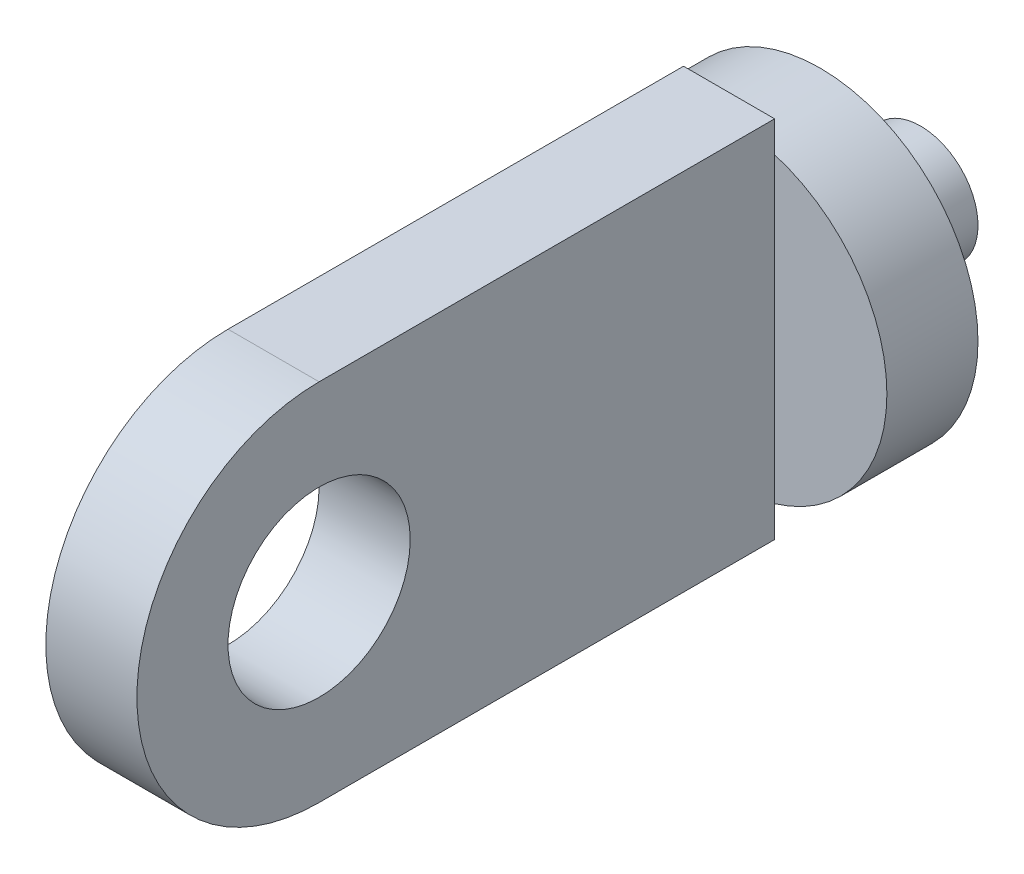
SolidWorks part; units mm, degrees
ref_plane "Front Plane" through (0, 0, 0) normal (0, 0, 1) x (1, 0, 0)
ref_plane "Top Plane" through (0, 0, 0) normal (0, 1, 0) x (1, 0, 0)
ref_plane "Right Plane" through (0, 0, 0) normal (1, 0, 0) x (0, 0, -1)
sketch "Sketch1" plane through (0, 0, 0) normal (1, 0, 0) x (0, 0, -1)
  circle A0 centre (0, 0) radius 12.7
  dimension "D1" = 25.4
extrude "Extrude-Thin1" add sketch "Sketch1" along normal blind 6.35 thin contours A0 thin type one direction reverse wall 6.35
ref_axis "Axis1" through (6.35, 0, 0) along (-1, 0, 0)
ref_plane "Plane1" through (3.175, 0, 0) normal (-1, 0, 0) x (0, 0, 1)
sketch "Sketch2" plane through (6.35, 0, 0) normal (1, 0, 0) x (0, 0, -1)
  line L0 (0, 12.7) -> (31.75, 12.7)
  line L1 (31.75, 12.7) -> (31.75, -12.7)
  line L2 (31.75, -12.7) -> (0, -12.7)
  circle A0 centre (0, 0) radius 12.7 construction
  arc A1 (0, -12.7) -> (0, 12.7) centre (0, 0) ccw
  dimension "D1" = 31.75
extrude "Boss-Extrude1" add sketch "Sketch2" against normal up to surface (6.35 mm away) up to face at (0, 0, -12.7)
sketch "Sketch3" plane through (0, 0, -31.75) normal (0, 0, -1) x (-1, 0, 0)
  line L0 (-3.175, -13.97) -> (-3.175, 13.97) construction
  line L1 (-6.35, 0) -> (0, 0) construction
  circle A0 centre (-3.175, 0) radius 11
  dimension "D1" = 22
extrude "Boss-Extrude2" add sketch "Sketch3" along normal blind 6.35
sketch "Sketch4" plane through (0, 0, -38.1) normal (0, 0, -1) x (-1, 0, 0)
  line L0 (-3.175, -13.97) -> (-3.175, 13.97) construction
  line L1 (-6.35, 0) -> (0, 0) construction
  circle A0 centre (-3.175, 0) radius 4
  circle A1 centre (-3.175, 0) radius 11 construction
  dimension "D1" = 8
extrude "Boss-Extrude3" add sketch "Sketch4" along normal blind 7
ref_axis "Axis2" through (3.175, 0, -45.1) along (0, 0, 1)
